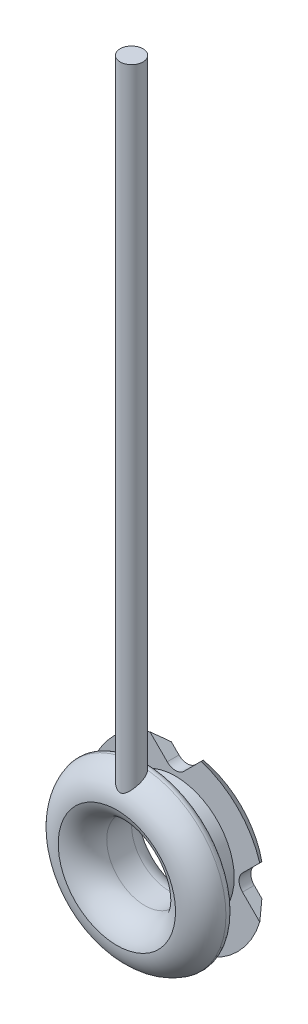
SolidWorks part; units mm, degrees
material "AISI 1035 Steel (SS)"
ref_plane "Front" through (0, 0, 0) normal (0, 0, 1) x (1, 0, 0)
ref_plane "Top" through (0, 0, 0) normal (0, 1, 0) x (1, 0, 0)
ref_plane "Right" through (0, 0, 0) normal (1, 0, 0) x (0, 0, -1)
sketch "Sketch1" plane through (0, 0, 0) normal (0, 0, 1) x (1, 0, 0)
  circle A0 centre (0, 0) radius 1
  circle A1 centre (0, 0) radius 0.65
  dimension "D1" = 2
  dimension "D2" = 1.3
extrude "Boss-Extrude1" add sketch "Sketch1" along normal blind 0.5
sketch "Sketch3" plane through (0, 0, 0.5) normal (0, 0, 1) x (1, 0, 0)
  circle A0 centre (0, 0) radius 1.5
  circle A1 centre (0, 0) radius 0.65
  dimension "D1" = 3
extrude "Boss-Extrude4" add sketch "Sketch3" along normal blind 0.5
sketch "Sketch4" plane through (0, 0, 0) normal (0, 0, -1) x (-1, 0, 0)
  line L0 (0, 1) -> (-0.4354, 1.4354)
  line L1 (0, 1) -> (0.4354, 1.4354)
  line L2 (1, 0) -> (1.4354, 0.4354)
  line L3 (1, 0) -> (1.4354, -0.4354)
  line L4 (0, -1.5) -> (0, 1.5) construction
  line L5 (-1.5, 0) -> (1.5, 0) construction
  line L6 (0, -1) -> (-0.4354, -1.4354)
  line L7 (0, -1) -> (0.4354, -1.4354)
  line L8 (-1, 0) -> (-1.4354, 0.4354)
  line L9 (-1, 0) -> (-1.4354, -0.4354)
  arc A0 (-0.4354, 1.4354) -> (-1.4354, 0.4354) centre (0, 0) ccw
  circle A1 centre (0, 0) radius 0.65
  circle A2 centre (0, 0) radius 1.5 construction
  arc A3 (1.4354, 0.4354) -> (0.4354, 1.4354) centre (0, 0) ccw
  arc A4 (0.4354, -1.4354) -> (1.4354, -0.4354) centre (0, 0) ccw
  arc A5 (-1.4354, -0.4354) -> (-0.4354, -1.4354) centre (0, 0) ccw
  dimension "D1" = 3
  dimension "D2" = 90
  dimension "D3" = 45
  dimension "D4" = 90
  dimension "D5" = 45
  dimension "D7" = 90
  dimension "D8" = 45
  dimension "D9" = 90
  dimension "D10" = 45
extrude "Boss-Extrude5" add sketch "Sketch4" along normal blind 0.2
fillet "Fillet4" radius 0.5 1 edges at (1.5, 0, 1)
fillet "Fillet5" radius 0.5 1 edges at (0.65, 0, 1)
fillet "Fillet6" radius 0.1 1 edges at (1.5, 0, 0.5)
chamfer "Chamfer2" distance 0.2 angle 45 4 edges at (-1.0607, -1.0607, -0.2) (-1.0607, 1.0607, -0.2) (1.0607, 1.0607, -0.2) (1.0607, -1.0607, -0.2)
fillet "Fillet8" radius 0.2 4 edges at (0, 1, -0.1) (1, 0, -0.1) (0, -1, -0.1) (-1, 0, -0.1)
fillet "Fillet9" radius 0.1 1 edges at (-0.9192, -0.9192, -0.2)
fillet "Fillet10" radius 0.3 1 edges at (-0.65, 0, -0.2)
ref_plane "Plane2" through (0, 0, 0.75) normal (0, 0, 1) x (1, 0, 0)
sketch "Sketch5" plane through (0, 0, 0.75) normal (0, 0, 1) x (1, 0, 0)
  line L0 (0, 12.0163) -> (0, 0.7163)
  dimension "D1" = 11.3
ref_plane "Plane3" through (0, 1, 0) normal (0, 1, 0) x (1, 0, 0)
sketch "Sketch6" plane through (0, 1, 0) normal (0, 1, 0) x (1, 0, 0)
  line L0 (1.3873, -0.5) -> (-1.3873, -0.5) construction
  circle A0 centre (0, -0.75) radius 0.195
  dimension "D2" = 0.39
  dimension "D1" = 0.25
sweep "Sweep2" add profiles "Sketch6" path "Sketch5"
